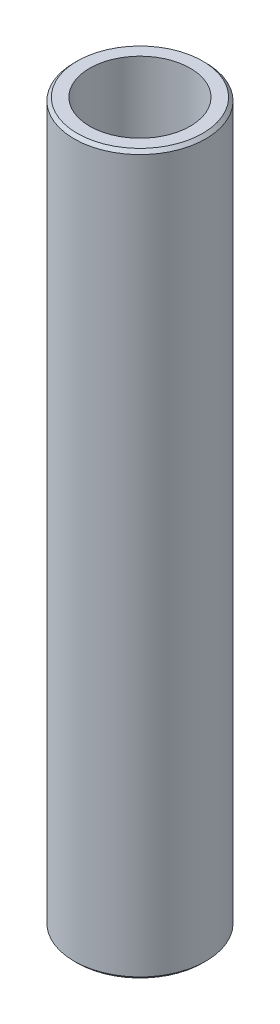
SolidWorks part; units mm, degrees
ref_plane "Front Plane" through (0, 0, 0) normal (0, 0, 1) x (1, 0, 0)
ref_plane "Top Plane" through (0, 0, 0) normal (0, 1, 0) x (1, 0, 0)
ref_plane "Right Plane" through (0, 0, 0) normal (1, 0, 0) x (0, 0, -1)
sketch "Sketch1" plane through (0, 0, 0) normal (0, 1, 0) x (1, 0, 0)
  circle A0 centre (0, 0) radius 55
  dimension "SHAFT_OD" = 110
extrude "Boss-Extrude1" add sketch "Sketch1" along normal blind 600
sketch "Sketch2" plane through (0, 0, 0) normal (0, 1, 0) x (1, 0, 0)
  circle A0 centre (0, 0) radius 41.9922
  dimension "BORE_D" = 83.9843
extrude "Cut-Extrude1" cut sketch "Sketch2" along normal through all
chamfer "Chamfer1" distance 2.6342 angle 45 2 edges at (0, 600, 55) (0, 0, 55)
